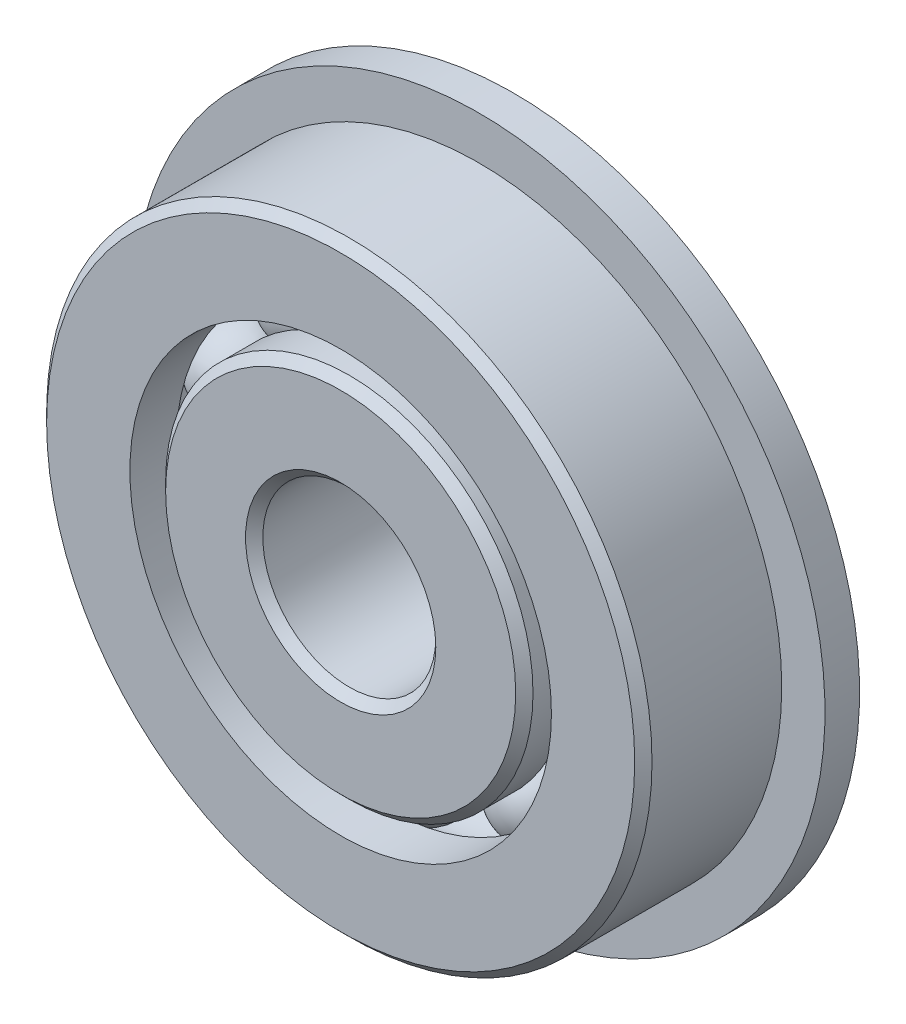
SolidWorks part; units mm, degrees
ref_plane "Front Plane" through (0, 0, 0) normal (0, 0, 1) x (1, 0, 0)
ref_plane "Top Plane" through (0, 0, 0) normal (0, 1, 0) x (1, 0, 0)
ref_plane "Right Plane" through (0, 0, 0) normal (1, 0, 0) x (0, 0, -1)
sketch "Sketch1" plane through (0, 0, 0) normal (1, 0, 0) x (0, 0, -1)
  line L0 (-3.175, 0) -> (3.175, 0) construction
  line L1 (0, 11.1125) -> (0, -11.1125) construction
  line L2 (2.8575, 11.1125) -> (-2.8575, 11.1125)
  line L3 (-2.8575, 11.1125) -> (-3.175, 10.795)
  line L4 (-3.175, 10.795) -> (-3.175, 7.7375)
  line L5 (-3.175, 7.7375) -> (-1.4723, 7.7375)
  line L6 (3.175, 7.7375) -> (1.4723, 7.7375)
  line L7 (3.175, 10.795) -> (3.175, 7.7375)
  line L8 (2.8575, 11.1125) -> (3.175, 10.795)
  line L9 (0, 11.1125) -> (0, 7.1438) construction
  line L10 (0, 7.1438) -> (0, 3.175) construction
  line L11 (3.175, 6.7437) -> (3.175, -6.7437) construction
  line L12 (-3.175, 3.175) -> (3.175, 3.175) construction
  line L13 (0, 5.5563) -> (0, 3.175) construction
  line L14 (0, 8.7312) -> (0, 11.1125) construction
  line L15 (3.175, 6.7437) -> (0, 6.7437) construction
  circle A1 centre (0, 7.1438) radius 1.5875 construction
  arc A2 (-1.4723, 7.7375) -> (1.4723, 7.7375) centre (0, 7.1438) cw
  point P14 (0, 3.175)
  point P22 (0, 5.5563)
  point P23 (0, 8.7313)
  dimension "D3" = 3.175
  dimension "Width" = 6.35
  dimension "OD" = 22.225
  dimension "D1" = 45
  dimension "D2" = 0.3175
  dimension "D4" = 13.4874
  dimension "D5" = 1.9876
  dimension "D6" = 0.9938
revolve "Revolve1" add sketch "Sketch1" angle 360 about L0
sketch "Sketch3" plane through (0, 0, 0) normal (1, 0, 0) x (0, 0, -1)
  line L1 (-3.175, 10.795) -> (-3.175, 7.7375) construction
  line L2 (-2.8575, 11.1125) -> (-3.175, 10.795) construction
  line L3 (-3.175, 6.55) -> (-3.175, 3.4925) construction
  line L4 (-3.175, 3.4925) -> (-3.175, 6.4262)
  line L5 (-3.175, 3.4925) -> (-2.8575, 3.175)
  line L6 (-2.8575, 3.175) -> (4.4577, 3.175)
  line L7 (-3.175, 10.795) -> (-3.175, -10.795) construction
  line L8 (4.4577, 3.175) -> (4.7752, 3.4925)
  line L9 (0, 0) -> (4.7752, 0) construction
  line L13 (2.8575, 11.1125) -> (3.175, 10.795) construction
  line L14 (-3.175, 6.4262) -> (-2.8575, 6.7437)
  line L15 (-2.8575, 6.7437) -> (-1.5363, 6.7437)
  line L16 (1.5363, 6.7437) -> (4.4577, 6.7437)
  line L17 (4.4577, 6.7437) -> (4.7752, 6.4262)
  line L18 (4.7752, 6.4262) -> (4.7752, 3.4925)
  circle A0 centre (0, 7.1438) radius 1.5875 construction
  arc A1 (-1.5363, 6.7437) -> (1.5363, 6.7437) centre (0, 7.1438) ccw
  dimension "D1" = 45
  dimension "Ring Wd" = 7.9502
  dimension "Inner Ring OD" = 13.4874
revolve "Revolve3" add sketch "Sketch3" angle 360 about L0
sketch "Sketch6" plane through (0, 0, 0) normal (1, 0, 0) x (0, 0, -1)
  line L1 (3.175, 7.7375) -> (1.905, 7.7375)
  line L2 (3.175, 7.7375) -> (3.175, 12.7)
  line L3 (3.175, 12.7) -> (1.905, 12.7)
  line L4 (1.905, 7.7375) -> (1.905, 12.7)
  line L5 (3.175, 0) -> (-3.175, 0) construction
  dimension "Flange OD" = 25.4
  dimension "Flange Thickness" = 1.27
revolve "Revolve6" add sketch "Sketch6" angle 360 about L5
sketch "Sketch4" plane through (0, 0, 0) normal (1, 0, 0) x (0, 0, -1)
  line L0 (-1.5875, 7.1438) -> (1.5875, 7.1438)
  circle A0 centre (0, 7.1438) radius 1.5875 construction
  arc A1 (1.5875, 7.1438) -> (-1.5875, 7.1438) centre (0, 7.1438) ccw
revolve "Revolve4" add sketch "Sketch4" angle 360 about L0
ref_axis "Axis1" through (0, 0, -3.175) along (0, 0, 1)
pattern_circular "CirPattern1" count 10 every 36 about axis through (0, 0, -3.175) along (0, 0, 1) of bodies 104
sketch "Sketch5" plane through (0, 0, 0) normal (1, 0, 0) x (0, 0, -1)
  line L0 (-3.175, 7.7375) -> (-1.4723, 7.7375) construction
  line L1 (-3.0162, 7.7375) -> (-1.5363, 7.7375)
  line L2 (-3.0162, 7.7375) -> (-3.0162, 6.7437)
  line L3 (-3.0162, 6.7437) -> (-1.5363, 6.7437)
  line L4 (-1.5363, 7.7375) -> (-1.5363, 6.7437)
  line L6 (3.175, 7.7375) -> (1.4723, 7.7375) construction
  line L7 (3.0162, 7.7375) -> (1.5363, 7.7375)
  line L8 (3.0162, 7.7375) -> (3.0162, 6.7437)
  line L9 (3.0162, 6.7437) -> (1.5363, 6.7437)
  line L10 (1.5363, 7.7375) -> (1.5363, 6.7437)
  line L12 (-2.8575, 11.1125) -> (-3.175, 10.795) construction
  line L13 (3.175, 6.7437) -> (0, 6.7437) construction
  line L15 (-2.8575, 6.7437) -> (-1.5363, 6.7437) construction
  line L16 (3.0162, 7.7375) -> (3.0162, 10.9538) construction
  line L17 (2.8575, 11.1125) -> (3.175, 10.795) construction
  point P18 (-3.0163, 10.9538)
revolve "Revolve5" [suppressed] add sketch "Sketch5" angle 360 about L0
equation "\"D2@Sketch1\" = \"Width@Sketch1\"*.05"
equation "\"D2@CirPattern1\" = 360/\"Balls@CirPattern1\""
equation "\"D4@Sketch1\"=\"Inner Ring OD@Sketch3\""
equation "\"D3@Sketch1\"=\"Width@Sketch1\"/2"
equation "\"D6@Sketch1\"=\"D5@Sketch1\"/2"
